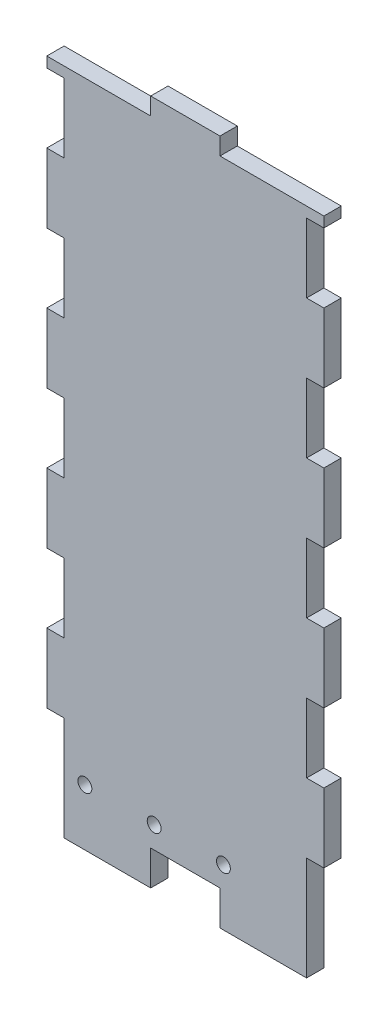
SolidWorks part; units mm, degrees
ref_plane "정면" through (0, 0, 0) normal (0, 0, 1) x (1, 0, 0)
ref_plane "윗면" through (0, 0, 0) normal (0, 1, 0) x (1, 0, 0)
ref_plane "우측면" through (0, 0, 0) normal (1, 0, 0) x (0, 0, -1)
sketch "스케치1" plane through (0, 0, 0) normal (0, 0, 1) x (1, 0, 0)
  line L1 (-40, 91.5) -> (40, 91.5)
  line L2 (-40, 91.5) -> (-40, -91.5)
  line L3 (-40, -91.5) -> (40, -91.5)
  line L4 (40, 91.5) -> (40, -91.5)
  line L5 (-40, 91.5) -> (40, -91.5) construction
  line L6 (-40, -91.5) -> (40, 91.5) construction
  point P0 (0, 0)
  dimension "D1" = 183
  dimension "D2" = 80
extrude "보스-돌출1" add sketch "스케치1" along normal blind 5
sketch "스케치2" plane through (0, 0, 5) normal (0, 0, 1) x (1, 0, 0)
  line L1 (-40, -91.5) -> (-35, -91.5)
  line L2 (-40, -91.5) -> (-40, -71.5)
  line L3 (-40, -71.5) -> (-35, -71.5)
  line L4 (-35, -91.5) -> (-35, -71.5)
  dimension "D1" = 5
  dimension "D2" = 20
extrude "컷-돌출1" cut sketch "스케치2" against normal up to next and the other way through all
pattern_linear "선형 패턴1" count 5 spacing 40 along (0, 1, 0) of "컷-돌출1"
sketch "스케치4" plane through (0, 0, 5) normal (0, 0, 1) x (1, 0, 0)
  line L1 (35, -91.5) -> (40, -91.5)
  line L2 (35, -91.5) -> (35, -71.5)
  line L3 (35, -71.5) -> (40, -71.5)
  line L4 (40, -91.5) -> (40, -71.5)
  dimension "D1" = 5
  dimension "D2" = 20
extrude "컷-돌출3" cut sketch "스케치4" against normal up to next
pattern_linear "선형 패턴4" count 5 spacing 40 along (0, 1, 0) of "컷-돌출3"
sketch "스케치5" plane through (0, 0, 5) normal (0, 0, 1) x (1, 0, 0)
  line L0 (40, 91.5) -> (-40, 91.5) construction
  line L1 (-10, 91.5) -> (10, 91.5)
  line L2 (-10, 91.5) -> (-10, 96.5)
  line L3 (-10, 96.5) -> (10, 96.5)
  line L4 (10, 91.5) -> (10, 96.5)
  line L5 (0, 159.4157) -> (0, 67.4362) construction
  point P10 (0, 113.4259)
  dimension "D1" = 5
  dimension "D2" = 20
extrude "보스-돌출2" add sketch "스케치5" against normal up to surface (5 mm away) up to face at (0, 7.65, 0)
sketch "스케치6" plane through (0, 0, 5) normal (0, 0, 1) x (1, 0, 0)
  line L0 (0, -80.4552) -> (0, -106.2956) construction
  line L1 (-35, -91.5) -> (35, -91.5) construction
  line L2 (-10, -101.5) -> (-35, -101.5)
  line L4 (10, -91.5) -> (10, -101.5)
  line L6 (-10, -91.5) -> (-10, -101.5)
  line L7 (-35, -101.5) -> (-35, -91.5)
  line L8 (-35, -91.5) -> (-10, -91.5)
  line L9 (10, -101.5) -> (35, -101.5)
  line L10 (35, -101.5) -> (35, -91.5)
  line L11 (35, -91.5) -> (10, -91.5)
  line L12 (-35, -71.5) -> (-35, -91.5) construction
  line L13 (35, -71.5) -> (35, -91.5) construction
  dimension "D1" = 20
  dimension "D2" = 10
extrude "보스-돌출3" add sketch "스케치6" against normal up to surface (5 mm away) up to face at (0, 15.5, 0)
sketch "스케치7" plane through (0, 0, 5) normal (0, 0, 1) x (1, 0, 0)
  line L0 (-35, -71.5) -> (-35, -101.5) construction
  line L1 (-10, -91.5) -> (10, -91.5) construction
  circle A0 centre (-29, -85.2) radius 2
  dimension "D3" = 4
  dimension "D1" = 6
  dimension "D2" = 6.3
extrude "컷-돌출4" cut sketch "스케치7" against normal up to next contours A0
pattern_linear "선형 패턴5" count 2 spacing 40 along (1, 0, 0) of "컷-돌출4"
pattern_linear "선형 패턴6" count 2 spacing 20 along (1, 0, 0) of "컷-돌출4"
